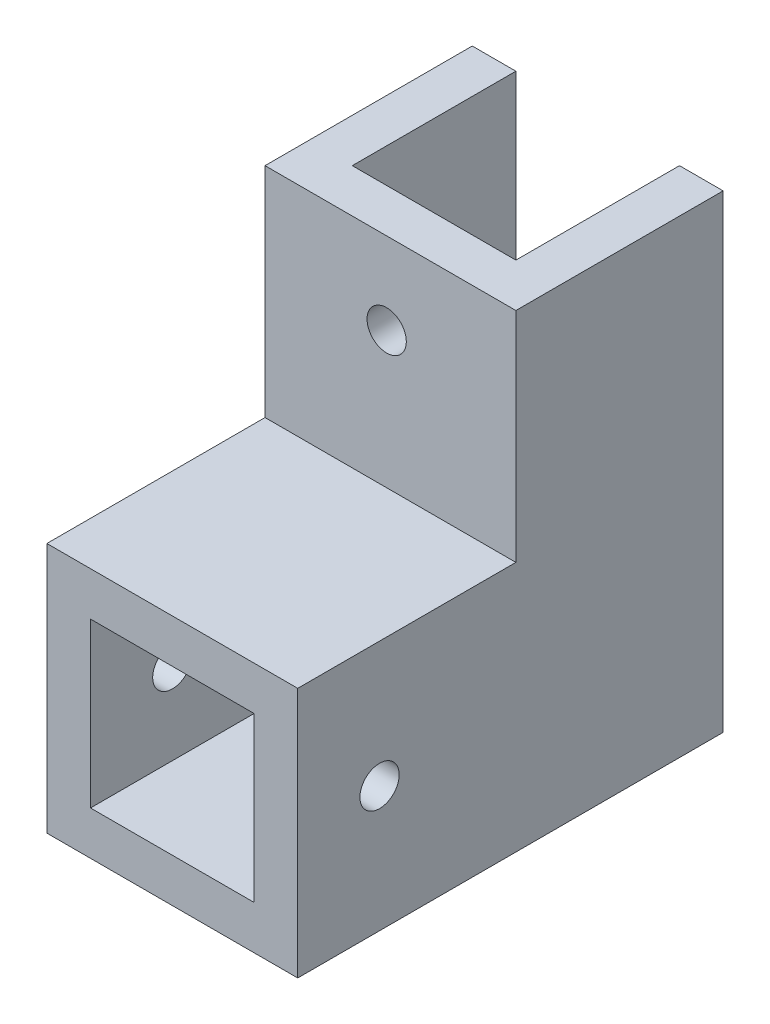
SolidWorks part; units mm, degrees
ref_plane "前视基准面" through (0, 0, 0) normal (0, 0, 1) x (1, 0, 0)
ref_plane "上视基准面" through (0, 0, 0) normal (0, 1, 0) x (1, 0, 0)
ref_plane "右视基准面" through (0, 0, 0) normal (1, 0, 0) x (0, 0, -1)
sketch "草图1" plane through (0, 0, 0) normal (0, 1, 0) x (1, 0, 0)
  line L1 (-11.1538, 14.2692) -> (-7.1538, 14.2692)
  line L2 (-11.1538, 14.2692) -> (-11.1538, -4.7308)
  line L3 (-11.1538, -4.7308) -> (-7.3846, -4.7308)
  line L4 (-7.1538, 14.2692) -> (-7.1538, -0.7308)
  line L5 (-7.3846, -4.7308) -> (11.8462, -4.7308)
  line L7 (-7.1538, -0.7308) -> (7.8462, -0.7308)
  line L8 (11.8462, -4.7308) -> (11.8462, -0.7308)
  line L10 (11.8462, -0.7308) -> (11.8462, 14.2692)
  line L11 (11.8462, 14.2692) -> (7.8462, 14.2692)
  line L12 (7.8462, -0.7308) -> (7.8462, 14.2692)
  dimension "D1" = 15
  dimension "D2" = 15
  dimension "D3" = 4
  dimension "D4" = 4
  dimension "D5" = 4
  dimension "D6" = 15
extrude "凸台-拉伸1" add sketch "草图1" along normal blind 20
sketch "草图2" plane through (0, 0, 0.7308) normal (0, 0, -1) x (-1, 0, 0)
  line L0 (7.1538, 20) -> (7.1538, 0) construction
  line L1 (-11.8462, 0) -> (11.1538, 0)
  line L2 (-11.8462, 0) -> (-11.8462, -23)
  line L3 (-11.8462, -23) -> (11.1538, -23)
  line L4 (11.1538, 0) -> (11.1538, -23)
  line L5 (-7.8462, -4) -> (7.1538, -4)
  line L6 (-7.8462, -4) -> (-7.8462, -19)
  line L7 (-7.8462, -19) -> (7.1538, -19)
  line L8 (7.1538, -4) -> (7.1538, -19)
  line L9 (-7.8462, 0) -> (7.1538, 0) construction
  dimension "D1" = 15
  dimension "D2" = 15
  dimension "D3" = 4
  dimension "D4" = 4
  dimension "D5" = 4
  dimension "D6" = 4
  dimension "D7" = 0
  dimension "D8" = 0
extrude "凸台-拉伸2" add sketch "草图2" against normal blind 24
sketch "草图3" plane through (0, 0, 0.7308) normal (0, 0, -1) x (-1, 0, 0)
  line L0 (-11.8462, -23) -> (11.1538, -23) construction
  line L1 (-11.8462, 0) -> (-7.8462, 0)
  line L2 (-11.8462, 0) -> (-11.8462, -23)
  line L3 (-11.8462, -23) -> (-7.8462, -23)
  line L4 (-7.8462, 0) -> (-7.8462, -23)
  line L6 (11.1538, 0) -> (7.1538, 0)
  line L7 (11.1538, 0) -> (11.1538, -23)
  line L8 (11.1538, -23) -> (7.1538, -23)
  line L9 (7.1538, 0) -> (7.1538, -23)
  dimension "D1" = 4
  dimension "D2" = 4
extrude "凸台-拉伸3" add sketch "草图3" along normal blind 15
sketch "草图4" plane through (0, 0, 4.7308) normal (0, 0, 1) x (1, 0, 0)
  line L0 (-11.1538, 20) -> (11.8462, 20) construction
  circle A0 centre (0, 12.5) radius 1.8
  dimension "D1" = 3.6
  dimension "D2" = 7.5
extrude "切除-拉伸1" cut sketch "草图4" against normal blind 15
sketch "草图5" plane through (11.8462, 0, 0) normal (1, 0, 0) x (0, 0, -1)
  line L0 (-24.7308, 0) -> (-24.7308, -23) construction
  circle A0 centre (-17.2308, -11.5) radius 1.8
  dimension "D1" = 3.6
  dimension "D2" = 7.5
extrude "切除-拉伸2" cut sketch "草图5" against normal blind 35
